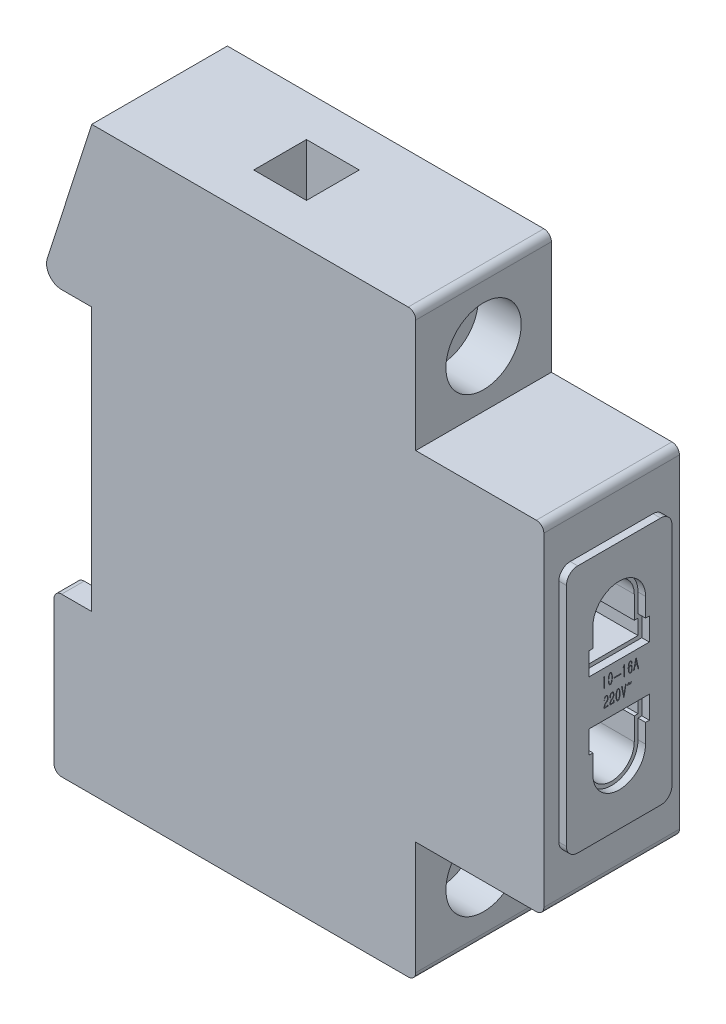
SolidWorks part; units mm, degrees
ref_plane "前视基准面" through (0, 0, 0) normal (0, 0, 1) x (1, 0, 0)
ref_plane "上视基准面" through (0, 0, 0) normal (0, 1, 0) x (1, 0, 0)
ref_plane "右视基准面" through (0, 0, 0) normal (1, 0, 0) x (0, 0, -1)
sketch "主截面" plane through (0, 0, 0) normal (0, 0, 1) x (1, 0, 0)
  line L0 (0, 1) -> (0, 20)
  line L1 (1, 21) -> (5, 21)
  line L2 (5, 21) -> (5, 56)
  line L3 (5, 56) -> (1, 56)
  line L4 (-0.9042, 58.6114) -> (5, 77)
  line L5 (5, 77) -> (47, 77)
  line L6 (48, 76) -> (48, 61)
  line L7 (48, 61) -> (64, 61)
  line L8 (65, 60) -> (65, 17)
  line L9 (64, 16) -> (48, 16)
  line L10 (48, 16) -> (48, 1)
  line L11 (47, 0) -> (1, 0)
  line L12 (65, 38.5) -> (-17.4492, 38.5) construction
  arc A0 (48, 76) -> (47, 77) centre (47, 76) ccw
  arc A1 (65, 60) -> (64, 61) centre (64, 60) ccw
  arc A2 (64, 16) -> (65, 17) centre (64, 17) ccw
  arc A3 (1, 56) -> (-0.9042, 58.6114) centre (1, 58) cw
  arc A4 (47, 0) -> (48, 1) centre (47, 1) ccw
  arc A5 (1, 0) -> (0, 1) centre (1, 1) cw
  arc A6 (1, 21) -> (0, 20) centre (1, 20) ccw
  point P16 (5, 38.5)
  point P23 (48, 77)
  point P26 (65, 61)
  point P29 (65, 16)
  point P34 (48, 0)
  point P37 (0, 0)
  point P40 (0, 21)
  dimension "D7" = 1
  dimension "D8" = 1
  dimension "D9" = 1
  dimension "D10" = 2
  dimension "D11" = 1
  dimension "D12" = 1
  dimension "D13" = 1
  dimension "D1" = 48
  dimension "D2" = 35
  dimension "D3" = 45
  dimension "D4" = 16
  dimension "D5" = 17
  dimension "D6" = 5
extrude "凸台-拉伸1" add sketch "主截面" along normal mid plane 18
sketch "草图2" plane through (65, 0, 0) normal (1, 0, 0) x (0, 0, -1)
  line L0 (-9, 38.5) -> (9, 38.5) construction
  line L1 (-9, 17) -> (-9, 60) construction
  line L2 (9, 17) -> (9, 60) construction
  line L3 (0, 60) -> (0, 17) construction
  line L4 (-9, 60) -> (9, 60) construction
  line L5 (-9, 17) -> (9, 17) construction
  line L7 (-5.5, 55) -> (5.5, 55)
  line L8 (-7, 53.5) -> (-7, 23.5)
  line L9 (-5.5, 22) -> (5.5, 22)
  line L10 (7, 53.5) -> (7, 23.5)
  line L11 (-7, 55) -> (7, 22) construction
  line L12 (-7, 22) -> (7, 55) construction
  arc A0 (5.5, 55) -> (7, 53.5) centre (5.5, 53.5) cw
  arc A1 (7, 23.5) -> (5.5, 22) centre (5.5, 23.5) cw
  arc A2 (-5.5, 22) -> (-7, 23.5) centre (-5.5, 23.5) cw
  arc A3 (-7, 53.5) -> (-5.5, 55) centre (-5.5, 53.5) cw
  point P12 (0, 38.5)
  dimension "D3" = 1.5
  dimension "D1" = 2
  dimension "D2" = 5
extrude "凸台-拉伸2" add sketch "草图2" along normal blind 1
sketch "2P插孔" plane through (66, 0, 0) normal (1, 0, 0) x (0, 0, -1)
  line L0 (0, 55) -> (0, 22) construction
  line L1 (5.5, 55) -> (-5.5, 55) construction
  line L2 (-5.5, 22) -> (5.5, 22) construction
  line L3 (-7, 38.5) -> (7, 38.5) construction
  line L4 (-7, 53.5) -> (-7, 23.5) construction
  line L5 (7, 23.5) -> (7, 53.5) construction
  line L6 (-3.5, 46.9921) -> (-3.5, 44.4921)
  line L7 (-4, 44.4921) -> (-3.5, 44.4921)
  line L8 (-4, 44.4921) -> (-4, 41.4921)
  line L9 (-4, 41.4921) -> (4, 41.4921)
  line L10 (4, 44.4921) -> (4, 41.4921)
  line L11 (-4, 44.4921) -> (4, 41.4921) construction
  line L12 (-4, 41.4921) -> (4, 44.4921) construction
  line L13 (3.5, 46.9921) -> (3.5, 44.4921)
  line L14 (3.5, 44.4921) -> (4, 44.4921)
  line L15 (-3, 46.9921) -> (-3, 43.9921)
  line L16 (-3.5, 43.9921) -> (-3, 43.9921)
  line L17 (-3.5, 43.9921) -> (-3.5, 41.9921)
  line L18 (-3.5, 41.9921) -> (3.5, 41.9921)
  line L19 (3.5, 43.9921) -> (3.5, 41.9921)
  line L20 (3, 43.9921) -> (3.5, 43.9921)
  line L21 (3, 46.9921) -> (3, 43.9921)
  line L22 (3.5, 32.5079) -> (4, 32.5079)
  line L23 (3, 33.0079) -> (3.5, 33.0079)
  line L24 (4, 32.5079) -> (4, 35.5079)
  line L25 (-4, 35.5079) -> (4, 35.5079)
  line L26 (-4, 32.5079) -> (-4, 35.5079)
  line L27 (-4, 32.5079) -> (-3.5, 32.5079)
  line L28 (-3.5, 30.0079) -> (-3.5, 32.5079)
  line L29 (3.5, 30.0079) -> (3.5, 32.5079)
  line L30 (3, 30.0079) -> (3, 33.0079)
  line L31 (3.5, 33.0079) -> (3.5, 35.0079)
  line L32 (-3.5, 35.0079) -> (3.5, 35.0079)
  line L33 (-3.5, 33.0079) -> (-3.5, 35.0079)
  line L34 (-3.5, 33.0079) -> (-3, 33.0079)
  line L35 (-3, 30.0079) -> (-3, 33.0079)
  arc A0 (3.5, 46.9921) -> (-3.5, 46.9921) centre (0, 46.9921) ccw
  arc A1 (3, 46.9921) -> (-3, 46.9921) centre (0, 46.9921) ccw
  arc A2 (3.5, 30.0079) -> (-3.5, 30.0079) centre (0, 30.0079) cw
  arc A3 (3, 30.0079) -> (-3, 30.0079) centre (0, 30.0079) cw
  point P12 (0, 42.9921)
  dimension "D3" = 7
  dimension "D1" = 8
  dimension "D2" = 3
  dimension "D4" = 4
  dimension "D5" = 0.5
extrude "切除-拉伸1" cut sketch "2P插孔" against normal blind 1 contours L10 L9 L8 L7 L6 A0 L13 L14 | L27 L28 A2 L29 L22 L24 L25 L26
extrude "切除-拉伸2" cut sketch "2P插孔<3>" against normal blind 10 contours L20 L19 L18 L17 L16 L15 A1 L21 | L33 L32 L31 L23 L30 A3 L35 L34
sketch "2P插孔<3>" plane through (66, 0, 0) normal (1, 0, 0) x (0, 0, -1) same geometry as "2P插孔"
hole_wizard "打孔尺寸(%根据)开槽圆柱头螺钉的类型1" positions "草图4" profile "草图5" counterbore size "M5" standard "GB"
sketch "草图4" plane through (48, 0, 0) normal (1, 0, 0) x (0, 0, -1)
  line L0 (-9, 68.5) -> (9, 68.5) construction
  line L1 (-9, 61) -> (-9, 76) construction
  line L2 (9, 61) -> (9, 76) construction
  line L4 (-9, 8.5) -> (9, 8.5) construction
  line L5 (-9, 1) -> (-9, 16) construction
  line L6 (9, 1) -> (9, 16) construction
  point P0 (0, 68.5)
  point P2 (0, 8.5)
sketch "草图5" plane through (48, 68.5, 0) normal (0, 1, 0) x (0, 0, -1)
  line L0 (0, 0) -> (0, 9.1524)
  line L1 (0, 9.1524) -> (2.75, 7.5)
  line L2 (2.75, 7.5) -> (2.75, 5.7)
  line L3 (2.75, 5.7) -> (5, 5.7)
  line L4 (5, 5.7) -> (5, 0)
  line L5 (5, 0) -> (0, 0)
  line L10 (0, 9.1524) -> (-2.75, 7.5) construction
  line L11 (0, -6.35) -> (0, 107.95) construction
  dimension "孔直径" = 5.5
  dimension "孔深度" = 7.5
  dimension "柱形沉头孔直径" = 10
  dimension "柱形沉头孔深度" = 5.7
  dimension "导头角度" = 118
sketch "草图6" plane through (0, 0, 0) normal (0, -1, 0) x (1, 0, 0)
  line L0 (-2.037, 0) -> (16.0194, 0) construction
  line L1 (1, 9) -> (47, 9) construction
  line L2 (5, -6) -> (-3, -6)
  line L3 (5, -6) -> (5, 6)
  line L4 (5, 6) -> (-3, 6)
  line L5 (-3, -6) -> (-3, 6)
  line L6 (5, -6) -> (-3, 6) construction
  line L7 (5, 6) -> (-3, -6) construction
  line L9 (5, 9) -> (5, -9) construction
  line L10 (1, 9) -> (1, -9) construction
  point P3 (1, 0)
  dimension "D1" = 3
extrude "切除-拉伸3" cut sketch "草图6" against normal up to surface (21 mm away) up to face at (3, 21, 0)
sketch "草图7" plane through (5, 0, 0) normal (-1, 0, 0) x (0, 0, 1)
  line L0 (-9, 38.5) -> (9, 38.5) construction
  line L1 (-9, 56) -> (-9, 21) construction
  line L2 (9, 56) -> (9, 21) construction
  line L3 (0, 56) -> (0, 0) construction
  line L4 (9, 56) -> (-9, 56) construction
  line L6 (2.5, 49.5) -> (-2.5, 49.5)
  line L7 (2.5, 49.5) -> (2.5, 42.5)
  line L8 (2.5, 42.5) -> (-2.5, 42.5)
  line L9 (-2.5, 49.5) -> (-2.5, 42.5)
  line L10 (2.5, 49.5) -> (-2.5, 42.5) construction
  line L11 (2.5, 42.5) -> (-2.5, 49.5) construction
  line L12 (2.5, 34.5) -> (-2.5, 34.5)
  line L13 (2.5, 34.5) -> (2.5, 26.5)
  line L14 (2.5, 26.5) -> (-2.5, 26.5)
  line L15 (-2.5, 34.5) -> (-2.5, 26.5)
  line L16 (2.5, 34.5) -> (-2.5, 26.5) construction
  line L17 (2.5, 26.5) -> (-2.5, 34.5) construction
  circle A0 centre (0, 38.5) radius 3
  point P13 (0, 46)
  point P18 (0, 30.5)
  dimension "D1" = 6
  dimension "D4" = 4
  dimension "D2" = 5
  dimension "D3" = 7
  dimension "D5" = 8
  dimension "D6" = 4
extrude "切除-拉伸4" cut sketch "草图7" against normal blind 10
sketch "草图8" plane through (0, 77, 0) normal (0, 1, 0) x (1, 0, 0)
  line L0 (-2.5623, 0) -> (51.607, 0) construction
  line L1 (48, -9) -> (48, 9) construction
  line L2 (28, 3.5) -> (21, 3.5)
  line L3 (28, 3.5) -> (28, -3.5)
  line L4 (28, -3.5) -> (21, -3.5)
  line L5 (21, 3.5) -> (21, -3.5)
  line L6 (28, 3.5) -> (21, -3.5) construction
  line L7 (28, -3.5) -> (21, 3.5) construction
  point P3 (24.5, 0)
  dimension "D1" = 20
  dimension "D2" = 7
extrude "切除-拉伸5" cut sketch "草图8" against normal blind 10
sketch "草图9" plane through (0, 0, 0) normal (0, -1, 0) x (1, 0, 0)
  line L0 (28, -3.5) -> (28, 3.5) construction
  line L1 (28, -3.5) -> (21, -3.5) construction
  line L2 (21, -3.5) -> (21, 3.5) construction
  line L3 (28, 3.5) -> (21, 3.5) construction
  line L4 (28, -3.5) -> (28, 3.5)
  line L5 (28, -3.5) -> (21, -3.5)
  line L6 (21, -3.5) -> (21, 3.5)
  line L7 (28, 3.5) -> (21, 3.5)
extrude "切除-拉伸6" cut sketch "草图9" against normal blind 10
sketch "文字1016A" plane through (66, 0, 0) normal (1, 0, 0) x (0, 0, -1)
  text T0 "10-16A" font "汉仪长仿宋体" height 1.5
extrude "切除-拉伸7" cut sketch "文字1016A" against normal blind 0.25
sketch "文字220V" plane through (66, 0, 0) normal (1, 0, 0) x (0, 0, -1)
  text T0 "220V~" font "汉仪长仿宋体" height 1.5
extrude "切除-拉伸8" cut sketch "文字220V" against normal blind 0.25
